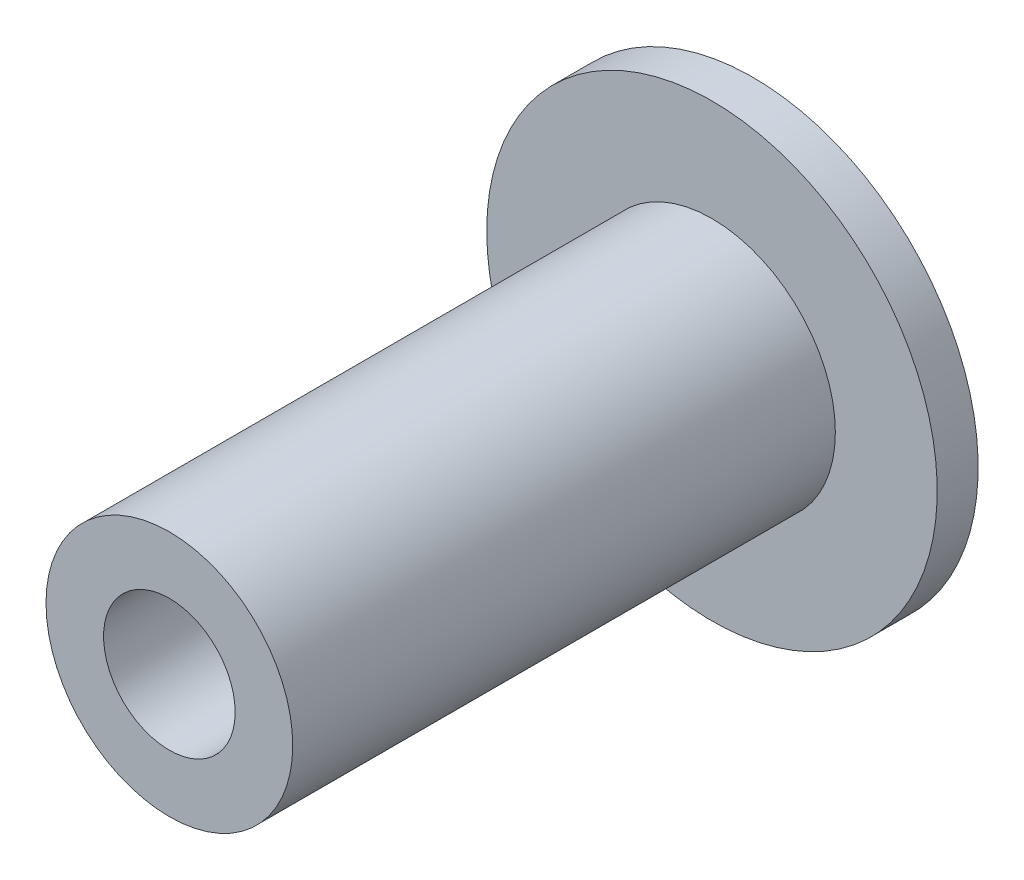
SolidWorks part; units mm, degrees
material "ABS"
ref_plane "Front Plane" through (0, 0, 0) normal (0, 0, 1) x (1, 0, 0)
ref_plane "Top Plane" through (0, 0, 0) normal (0, 1, 0) x (1, 0, 0)
ref_plane "Right Plane" through (0, 0, 0) normal (1, 0, 0) x (0, 0, -1)
sketch "Sketch1" plane through (0, 0, 0) normal (0, 0, 1) x (1, 0, 0)
  circle A0 centre (0, 0) radius 6.025
extrude "Boss-Extrude1" add sketch "Sketch1" along normal blind 10
sketch "Sketch2" plane through (0, 0, 10) normal (0, 0, 1) x (1, 0, 0)
  line L0 (0, -3.1496) -> (0, 3.1496) construction
  line L1 (2.7276, -1.5748) -> (-2.7276, 1.5748) construction
  line L2 (-2.7276, -1.5748) -> (2.7276, 1.5748) construction
  line L3 (0, 3.1496) -> (0.7493, 2.8395)
  line L4 (0.7493, 2.8395) -> (0.7846, 1.3589)
  line L5 (0.7846, 1.3589) -> (2.0845, 2.0687)
  line L6 (2.0845, 2.0687) -> (2.7276, 1.5748)
  line L7 (-1.9007, -3.2922) -> (2.1995, 3.8096) construction
  line L8 (2.7276, 1.5748) -> (2.8338, 0.7709)
  line L9 (2.8338, 0.7709) -> (1.5691, 0)
  line L10 (1.5691, 0) -> (2.8338, -0.7709)
  line L11 (2.8338, -0.7709) -> (2.7276, -1.5748)
  line L12 (2.7276, -1.5748) -> (2.0845, -2.0687)
  line L13 (2.0845, -2.0687) -> (0.7846, -1.3589)
  line L14 (0.7846, -1.3589) -> (0.7493, -2.8395)
  line L15 (0.7493, -2.8395) -> (0, -3.1496)
  line L16 (0, -3.1496) -> (-0.7493, -2.8395)
  line L17 (-0.7493, -2.8395) -> (-0.7846, -1.3589)
  line L18 (-0.7846, -1.3589) -> (-2.0845, -2.0687)
  line L19 (-2.0845, -2.0687) -> (-2.7276, -1.5748)
  line L20 (-2.7276, -1.5748) -> (-2.8338, -0.7709)
  line L21 (-2.8338, -0.7709) -> (-1.5691, 0)
  line L22 (-1.5691, 0) -> (-2.8338, 0.7709)
  line L23 (-2.8338, 0.7709) -> (-2.7276, 1.5748)
  line L24 (-2.7276, 1.5748) -> (-2.0845, 2.0687)
  line L25 (-2.0845, 2.0687) -> (-0.7846, 1.3589)
  line L26 (-0.7846, 1.3589) -> (-0.7493, 2.8395)
  line L27 (-0.7493, 2.8395) -> (0, 3.1496)
  circle A0 centre (0, 0) radius 3.1496
  point P7 (0, 0)
  point P9 (0, 0)
  point P12 (0, 0)
  point P18 (0, 0)
  point P45 (0, 0)
  dimension "D1" = 60
  dimension "D4" = 6.2992
  dimension "D2" = 60
  dimension "D3" = 1.7907
  dimension "D5" = 150
  dimension "D6" = 6
  dimension "D7" = 1.4986
extrude "Cut-Extrude1" [suppressed] cut sketch "Sketch2" against normal blind 10 contours L27 L26 L25 L24 L23 L22 L21 L20 L19 L18 L17 L16 L15 L14 L13 L12 L11 L10 L9 L8 L6 L5 L4 L3
sketch "Sketch3" plane through (0, 0, 10) normal (0, 0, 1) x (1, 0, 0)
  circle A0 centre (0, 0) radius 6.025
extrude "Boss-Extrude2" add sketch "Sketch3" along normal blind 16.5
sketch "Sketch4" plane through (0, 0, 26.5) normal (0, 0, 1) x (1, 0, 0)
  circle A0 centre (0, 0) radius 3.1496
extrude "Cut-Extrude2" [suppressed] cut sketch "Sketch4" against normal blind 16.5
sketch "Sketch5" plane through (0, 0, 0) normal (0, 0, -1) x (-1, 0, 0)
  circle A0 centre (0, 0) radius 11
extrude "Boss-Extrude3" add sketch "Sketch5" along normal blind 2
sketch "Sketch6" plane through (0, 0, 26.5) normal (0, 0, 1) x (1, 0, 0)
  circle A0 centre (0, 0) radius 3.2131
extrude "Cut-Extrude3" cut sketch "Sketch6" against normal blind 25.4
